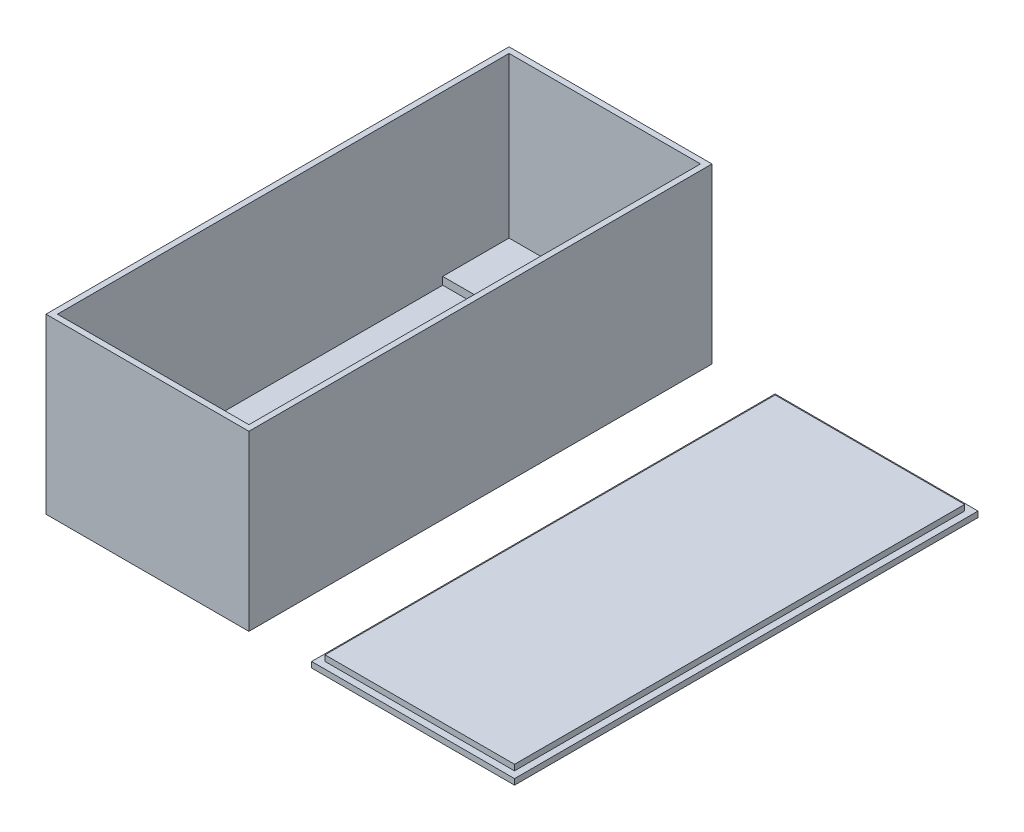
SolidWorks part; units mm, degrees
ref_plane "Plano frontal" through (0, 0, 0) normal (0, 0, 1) x (1, 0, 0)
ref_plane "Plano superior" through (0, 0, 0) normal (0, 1, 0) x (1, 0, 0)
ref_plane "Plano direito" through (0, 0, 0) normal (1, 0, 0) x (0, 0, -1)
sketch "Esboço1" plane through (0, 0, 0) normal (0, 1, 0) x (1, 0, 0)
  line L0 (-60.9055, -49.0726) -> (-18.4055, 47.9274) construction
  line L1 (-60.9055, 47.9274) -> (-18.4055, 47.9274)
  line L2 (-60.9055, 47.9274) -> (-60.9055, -49.0726)
  line L3 (-60.9055, -49.0726) -> (-18.4055, -49.0726)
  line L4 (-18.4055, 47.9274) -> (-18.4055, -49.0726)
  line L5 (-60.9055, 47.9274) -> (-18.4055, -49.0726) construction
  line L6 (-60.9055, 33.9274) -> (-18.4055, 33.9274) construction
  line L8 (-19.6055, 47.9274) -> (-19.6055, 33.9274) construction
  line L9 (-59.7055, 33.9274) -> (-59.7055, 47.9274) construction
  line L16 (-44.1555, -41.0726) -> (-42.6555, -41.0726)
  line L17 (-44.1555, -41.0726) -> (-44.1555, -44.0726)
  line L18 (-44.1555, -44.0726) -> (-42.6555, -44.0726)
  line L19 (-42.6555, -41.0726) -> (-42.6555, -44.0726)
  line L20 (-36.6555, -44.0726) -> (-35.1555, -44.0726)
  line L21 (-36.6555, -44.0726) -> (-36.6555, -41.0726)
  line L22 (-36.6555, -41.0726) -> (-35.1555, -41.0726)
  line L23 (-35.1555, -44.0726) -> (-35.1555, -41.0726)
  line L24 (-46.7835, -39.8726) -> (-32.5275, -39.8726)
  line L25 (-46.7835, -39.8726) -> (-46.7835, -45.2726)
  line L26 (-46.7835, -45.2726) -> (-32.5275, -45.2726)
  line L27 (-32.5275, -39.8726) -> (-32.5275, -45.2726)
  line L28 (-42.6555, -33.8726) -> (-36.6555, -33.8726)
  line L29 (-42.6555, -33.8726) -> (-42.6555, -49.0726)
  line L30 (-42.6555, -49.0726) -> (-36.6555, -49.0726)
  line L31 (-36.6555, -33.8726) -> (-36.6555, -49.0726)
  circle A0 centre (-39.6555, -37.0726) radius 1.6
  point P4 (-39.6555, -0.5726)
  point P5 (-39.6555, -49.0726)
  point P18 (-39.6555, -45.2726)
  point P27 (-46.7835, -42.5726)
  point P28 (-44.1555, -42.5726)
  point P33 (-39.6555, -33.8726)
  point P34 (-42.6555, -42.5726)
  point P35 (-35.1555, -42.5726)
  dimension "D3" = 14
  dimension "D6" = 12
  dimension "D7" = 6
  dimension "D8" = 3.2
  dimension "D11" = 3.2
  dimension "D1" = 42.5
  dimension "D2" = 97
  dimension "D4" = 1.2
  dimension "D5" = 1.2
  dimension "D9" = 3
  dimension "D10" = 5
extrude "Ressalto-extrusão2" add sketch "Esboço1" along normal blind 36.3 contours L3 L4 L1 L2
sketch "Esboço2" plane through (0, 36.3, 0) normal (0, 1, 0) x (1, 0, 0)
  line L0 (-59.7055, 46.7274) -> (-19.6055, -47.8726) construction
  line L1 (-59.7055, 46.7274) -> (-19.6055, 46.7274)
  line L2 (-59.7055, 46.7274) -> (-59.7055, -47.8726)
  line L3 (-59.7055, -47.8726) -> (-19.6055, -47.8726)
  line L4 (-19.6055, 46.7274) -> (-19.6055, -47.8726)
  line L5 (-59.7055, -47.8726) -> (-19.6055, 46.7274) construction
  line L6 (-60.9055, -49.0726) -> (-18.4055, 47.9274) construction
  line L7 (-18.4055, 47.9274) -> (-60.9055, 47.9274) construction
  line L8 (-60.9055, 47.9274) -> (-18.4055, -49.0726) construction
  point P4 (-39.6555, -0.5726)
  point P13 (-39.6555, -0.5726)
  dimension "D1" = 94.6
  dimension "D2" = 40.1
extrude "Corte-extrusão1" cut sketch "Esboço2" against normal blind 35.1 contours L3 L4 L1 L2
sketch "Esboço3" plane through (0, 1.2, 0) normal (0, 1, 0) x (1, 0, 0)
  line L0 (-59.7055, 32.7274) -> (-19.6055, 32.7274) construction
  line L1 (-59.7055, 46.7274) -> (-59.7055, -47.8726) construction
  line L2 (-19.6055, 46.7274) -> (-19.6055, -47.8726) construction
  line L3 (-59.7055, 46.7274) -> (-19.6055, 46.7274) construction
  line L4 (-39.6555, 32.7274) -> (-39.6555, 46.7274) construction
  line L5 (-39.6555, 39.7274) -> (-59.7055, 39.7274) construction
  line L6 (-39.6555, 39.7274) -> (-19.6055, 39.7274) construction
  circle A0 centre (-49.6805, 39.7274) radius 3.4
  circle A2 centre (-29.6305, 39.7274) radius 1
  circle A3 centre (-39.6555, 39.7274) radius 2.8
  point P12 (-49.6805, 39.7274)
  point P14 (-29.6305, 39.7274)
  point P15 (-39.6555, 39.7274)
  point P20 (-39.6555, 46.7274)
  dimension "D1" = 14
extrude "Corte-extrusão2" cut sketch "Esboço3" against normal through all
sketch "Esboço5" plane through (0, 1.2, 0) normal (0, 1, 0) x (1, 0, 0)
  line L0 (-19.6055, 46.7274) -> (-19.6055, -47.8726) construction
  line L2 (-59.7055, 46.7274) -> (-19.6055, 46.7274)
  line L3 (-59.7055, 46.7274) -> (-59.7055, 32.8274)
  line L4 (-59.7055, 32.8274) -> (-19.6055, 32.8274)
  line L5 (-19.6055, 46.7274) -> (-19.6055, 32.8274)
  circle A0 centre (-29.6305, 39.7274) radius 1 construction
  circle A1 centre (-39.6555, 39.7274) radius 2.8 construction
  circle A2 centre (-49.6805, 39.7274) radius 3.4 construction
  circle A3 centre (-29.6305, 39.7274) radius 1
  circle A4 centre (-39.6555, 39.7274) radius 2.8
  circle A5 centre (-49.6805, 39.7274) radius 3.4
  circle A7 centre (-39.6555, 39.7274) radius 3.8707
  circle A8 centre (-29.6305, 39.7274) radius 6.1
  circle A9 centre (-29.6305, 39.7274) radius 6.9
  dimension "D1" = 6.9
extrude "Ressalto-extrusão6" add sketch "Esboço5" along normal blind 1.6 contours L4 L5 L2 L3 | A5 | A7 | A8
extrude "Ressalto-extrusão8" add sketch "Esboço5<7>" along normal blind 6 contours A4 | A7 | A9 | A8
sketch "Esboço5<7>" plane through (0, 1.2, 0) normal (0, 1, 0) x (1, 0, 0) same geometry as "Esboço5"
sketch "Esboço6" plane through (0, 0, 0) normal (0, 1, 0) x (1, 0, 0)
  line L0 (-60.9055, 47.9274) -> (-18.4055, 47.9274) construction
  line L1 (-5.1804, 47.9274) -> (37.3196, 47.9274)
  line L2 (-5.1804, 47.9274) -> (-5.1804, -49.1549)
  line L3 (-5.1804, -49.1549) -> (37.3196, -49.1549)
  line L4 (37.3196, 47.9274) -> (37.3196, -49.1549)
  line L5 (-5.1804, -49.1549) -> (37.3196, 47.9274) construction
  line L6 (-5.1804, 47.9274) -> (37.3196, -49.1549) construction
  line L8 (-3.7804, 46.5274) -> (35.9196, 46.5274)
  line L9 (-3.7804, 46.5274) -> (-3.7804, -47.7549)
  line L10 (-3.7804, -47.7549) -> (35.9196, -47.7549)
  line L11 (35.9196, 46.5274) -> (35.9196, -47.7549)
  line L12 (-3.7804, -47.7549) -> (35.9196, 46.5274) construction
  line L13 (-3.7804, 46.5274) -> (35.9196, -47.7549) construction
  point P6 (16.0696, -0.6137)
  point P11 (16.0696, -0.6137)
extrude "Ressalto-extrusão11" add sketch "Esboço6" along normal blind 1.2 separate body contours L1 L4 L3 L2
extrude "Ressalto-extrusão12" add sketch "Esboço6<4>" along normal blind 1.2 contours L8 L11 L10 L9
sketch "Esboço6<4>" plane through (0, 0, 0) normal (0, 1, 0) x (1, 0, 0) same geometry as "Esboço6"
extrude "Ressalto-extrusão13" add sketch "Esboço6<5>" along normal blind 2.4 contours L8 L11 L10 L9
sketch "Esboço6<5>" plane through (0, 0, 0) normal (0, 1, 0) x (1, 0, 0) same geometry as "Esboço6"
extrude "Corte-extrusão10" cut sketch "Esboço1<8>" along normal through all contours L20 L23 L22 L21 | L16 L19 L18 L17 | A0
sketch "Esboço1<8>" plane through (0, 0, 0) normal (0, 1, 0) x (1, 0, 0) same geometry as "Esboço1"
extrude "Ressalto-extrusão14" add sketch "Esboço1<10>" along normal blind 2.8 contours L24 L27 L26 L25 | L16 L19 L18 L17 | L20 L23 L22 L21 | A0 | L28 L31 L30 L29
sketch "Esboço1<10>" plane through (0, 0, 0) normal (0, 1, 0) x (1, 0, 0) same geometry as "Esboço1"
